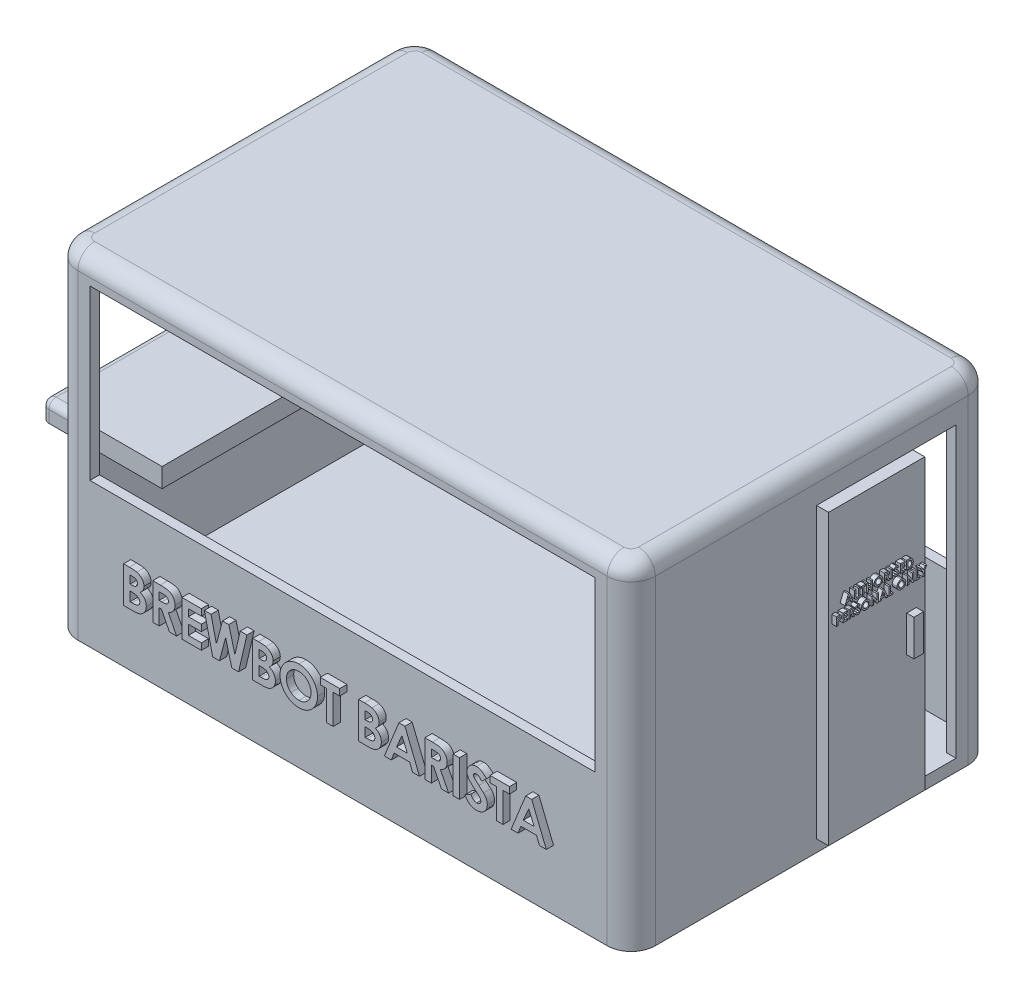
SolidWorks part; units mm, degrees
ref_plane "Front Plane" through (0, 0, 0) normal (0, 0, 1) x (1, 0, 0)
ref_plane "Top Plane" through (0, 0, 0) normal (0, 1, 0) x (1, 0, 0)
ref_plane "Right Plane" through (0, 0, 0) normal (1, 0, 0) x (0, 0, -1)
sketch "Sketch1" plane through (0, 0, 0) normal (0, 1, 0) x (1, 0, 0)
  line L1 (0, 0) -> (2400, 0)
  line L2 (0, 0) -> (0, 1500)
  line L3 (0, 1500) -> (2400, 1500)
  line L4 (2400, 0) -> (2400, 1500)
  dimension "D1" = 2400
  dimension "D2" = 1500
extrude "Boss-Extrude1" add sketch "Sketch1" along normal blind 50
sketch "Sketch2" plane through (0, 50, 0) normal (0, 1, 0) x (1, 0, 0)
  line L14 (2360, 40) -> (2360, 1460)
  line L15 (40, 40) -> (2360, 40)
  line L16 (40, 1460) -> (40, 40)
  line L17 (2360, 1460) -> (40, 1460)
  line L18 (2360, 40) -> (2360, 1460)
  line L19 (40, 40) -> (2360, 40)
  line L20 (40, 1460) -> (40, 40)
  line L21 (2360, 1460) -> (40, 1460)
  line M5 (0, 1500) -> (0, 0)
  line M6 (0, 0) -> (2400, 0)
  line M7 (2400, 0) -> (2400, 1500)
  line M8 (2400, 1500) -> (0, 1500)
  dimension "D1" = 40
extrude "Boss-Extrude2" add sketch "Sketch2" along normal blind 1300 contours L21 L18 L19 L20 M8 M5 M6 M7 region at (1200, 50, -1471.6981)
sketch "Sketch3" plane through (0, 1350, 0) normal (0, 1, 0) x (1, 0, 0)
  line L1 (0, 1500) -> (2400, 1500)
  line L2 (0, 1500) -> (0, 0)
  line L3 (0, 0) -> (2400, 0)
  line L4 (2400, 1500) -> (2400, 0)
extrude "Boss-Extrude3" add sketch "Sketch3" along normal blind 50
sketch "Sketch4" plane through (0, 0, 0) normal (0, 0, 1) x (1, 0, 0)
  line L0 (1200, 1300) -> (1200, 1400) construction
  line L1 (150, 1300) -> (2250, 1300)
  line L2 (150, 1300) -> (150, 600)
  line L3 (150, 600) -> (2250, 600)
  line L4 (2250, 1300) -> (2250, 600)
  line L5 (0, 1400) -> (2400, 1400) construction
  line L6 (0, 1400) -> (0, 0) construction
  dimension "D1" = 700
  dimension "D2" = 100
  dimension "D3" = 150
extrude "Cut-Extrude1" cut sketch "Sketch4" against normal up to surface (1500 mm away) up to face at (1200, 700, -1500)
sketch "Sketch5" plane through (0, 0, 0) normal (-1, 0, 0) x (0, 0, 1)
  line L0 (-750, 1150) -> (-750, 1400) construction
  line L1 (-1350, 1150) -> (-150, 1150)
  line L2 (-1350, 1150) -> (-1350, 650)
  line L3 (-1350, 650) -> (-150, 650)
  line L4 (-150, 1150) -> (-150, 650)
  line L5 (-1500, 1400) -> (0, 1400) construction
  line L6 (-1500, 1400) -> (-1500, 0) construction
  dimension "D1" = 150
  dimension "D2" = 500
  dimension "D3" = 250
extrude "Cut-Extrude2" cut sketch "Sketch5" against normal up to surface (40 mm away) up to face at (40, 700, -750)
sketch "Sketch6" plane through (0, 0, 0) normal (0, 0, 1) x (1, 0, 0)
  line L0 (0, 250) -> (2400, 250) construction
  line L1 (0, 1400) -> (0, 0) construction
  line L2 (2400, 1400) -> (2400, 0) construction
  line L3 (0, 0) -> (2400, 0) construction
  text T0 "<b>BREWBOT BARISTA</b>" font "Century Gothic" height 150
  dimension "D1" = 250
extrude "Boss-Extrude4" add sketch "Sketch6" along normal blind 30
sketch "Sketch7" plane through (0, 0, -1500) normal (0, 0, 1) x (1, 0, 0)
  line L0 (150, 600) -> (2250, 600) construction
  line L1 (1175, 600) -> (1225, 600)
  line L2 (1175, 600) -> (1175, 900)
  line L3 (1175, 900) -> (1225, 900)
  line L4 (1225, 600) -> (1225, 900)
  point P6 (1200, 600)
  dimension "D1" = 50
  dimension "D2" = 300
extrude "Boss-Extrude5" add sketch "Sketch7" along normal up to surface (40 mm away) separate body up to face at (1200, 950, -1460)
sketch "Sketch8" plane through (0, 0, -1500) normal (0, 0, -1) x (-1, 0, 0)
  line L1 (-1425, 900) -> (-975, 900)
  line L2 (-1425, 900) -> (-1425, 650)
  line L3 (-1425, 650) -> (-975, 650)
  line L4 (-975, 900) -> (-975, 650)
  line L5 (-1225, 900) -> (-1175, 900) construction
  point P6 (-1200, 900)
  dimension "D1" = 450
  dimension "D2" = 250
extrude "Boss-Extrude6" add sketch "Sketch8" along normal blind 30 separate body
sketch "Sketch9" plane through (0, 0, 0) normal (-1, 0, 0) x (0, 0, 1)
  line L0 (-150, 650) -> (-150, 1150) construction
  line L1 (-1350, 650) -> (-150, 650)
  line L2 (-1350, 650) -> (-1350, 570)
  line L3 (-1350, 570) -> (-150, 570)
  line L4 (-150, 650) -> (-150, 570)
  dimension "D1" = 80
extrude "Boss-Extrude7" add sketch "Sketch9" along normal blind 200 and the other way blind 300 contours L2 L1 L4 L3
fillet "Fillet1" radius 100 4 edges at (2400, 700, 0) (2400, 700, -1500) (0, 700, -1500) (0, 700, 0)
fillet "Fillet3" radius 30 5 edges at (-100, 650, -1350) (-200, 610, -1350) (-200, 610, -150) (-200, 650, -750) (-100, 650, -150)
sketch "Sketch10" plane through (2400, 0, 0) normal (1, 0, 0) x (0, 0, -1)
  line L0 (100, 0) -> (1400, 0) construction
  line L1 (1350, 50) -> (950, 50)
  line L2 (1350, 50) -> (1350, 1250)
  line L3 (1350, 1250) -> (950, 1250)
  line L4 (950, 50) -> (950, 1250)
  line L5 (1400, 0) -> (1400, 1400) construction
  dimension "D1" = 400
  dimension "D2" = 50
  dimension "D3" = 50
  dimension "D4" = 1200
extrude "Cut-Extrude3" cut sketch "Sketch10" against normal up to surface (40 mm away) up to face at (2360, 700, -750)
sketch "Sketch11" plane through (2400, 0, 0) normal (1, 0, 0) x (0, 0, -1)
  line L0 (1460, 50) -> (40, 50) construction
  line L1 (770, 1250) -> (1170, 1250)
  line L2 (770, 1250) -> (770, 50)
  line L3 (770, 50) -> (1170, 50)
  line L4 (1170, 1250) -> (1170, 50)
  line L5 (1350, 1250) -> (950, 1250) construction
  line L6 (950, 50) -> (1350, 50) construction
  line L7 (1350, 50) -> (1350, 1250) construction
  dimension "D1" = 180
extrude "Boss-Extrude10" add sketch "Sketch11" along normal blind 50 separate body
sketch "Sketch12" plane through (2450, 0, 0) normal (1, 0, 0) x (0, 0, -1)
  line L0 (1135, 650) -> (1170, 650) construction
  line L1 (1135, 725) -> (1095, 725)
  line L2 (1135, 725) -> (1135, 575)
  line L3 (1135, 575) -> (1095, 575)
  line L4 (1095, 725) -> (1095, 575)
  line L5 (1170, 50) -> (1170, 1250) construction
  dimension "D1" = 40
  dimension "D2" = 150
  dimension "D3" = 35
extrude "Boss-Extrude11" add sketch "Sketch12" along normal blind 30
sketch "Sketch13" plane through (2450, 0, 0) normal (1, 0, 0) x (0, 0, -1)
  line L0 (770, 900) -> (1170, 900) construction
  line L1 (770, 1250) -> (770, 50) construction
  line L2 (1170, 50) -> (1170, 1250) construction
  line L3 (1170, 1250) -> (770, 1250) construction
  text T0 "<b>AUTHORISED </b>\r\n<b>PERSONAL ONLY</b>" font "Century Gothic" height 35
  dimension "D1" = 350
extrude "Boss-Extrude12" add sketch "Sketch13" along normal blind 20
sketch "Sketch14" plane through (0, 0, 0) normal (-1, 0, 0) x (0, 0, 1)
  text T0 "PICK UP POINT" font "Century Gothic" height 100
extrude "Boss-Extrude13" add sketch "Sketch14" along normal blind 20
fillet "Fillet4" radius 70 8 edges at (29.2893, 1400, -29.2893) (0, 1400, -750) (29.2893, 1400, -1470.7107) (1200, 1400, -1500) (2370.7107, 1400, -1470.7107) (2400, 1400, -750) (2370.7107, 1400, -29.2893) (1200, 1400, 0)
sketch "Sketch16" plane through (0, 0, -1500) normal (0, 0, -1) x (-1, 0, 0)
  line L0 (-2300, 250) -> (-100, 250) construction
  line L1 (-2300, 1330) -> (-2300, 0) construction
  line L2 (-100, 0) -> (-100, 1330) construction
  line L3 (-2300, 0) -> (-100, 0) construction
  text T0 "BREWBOT BARISTA" font "Century Gothic" height 150
  dimension "D1" = 250
extrude "Boss-Extrude14" add sketch "Sketch16" along normal blind 30
